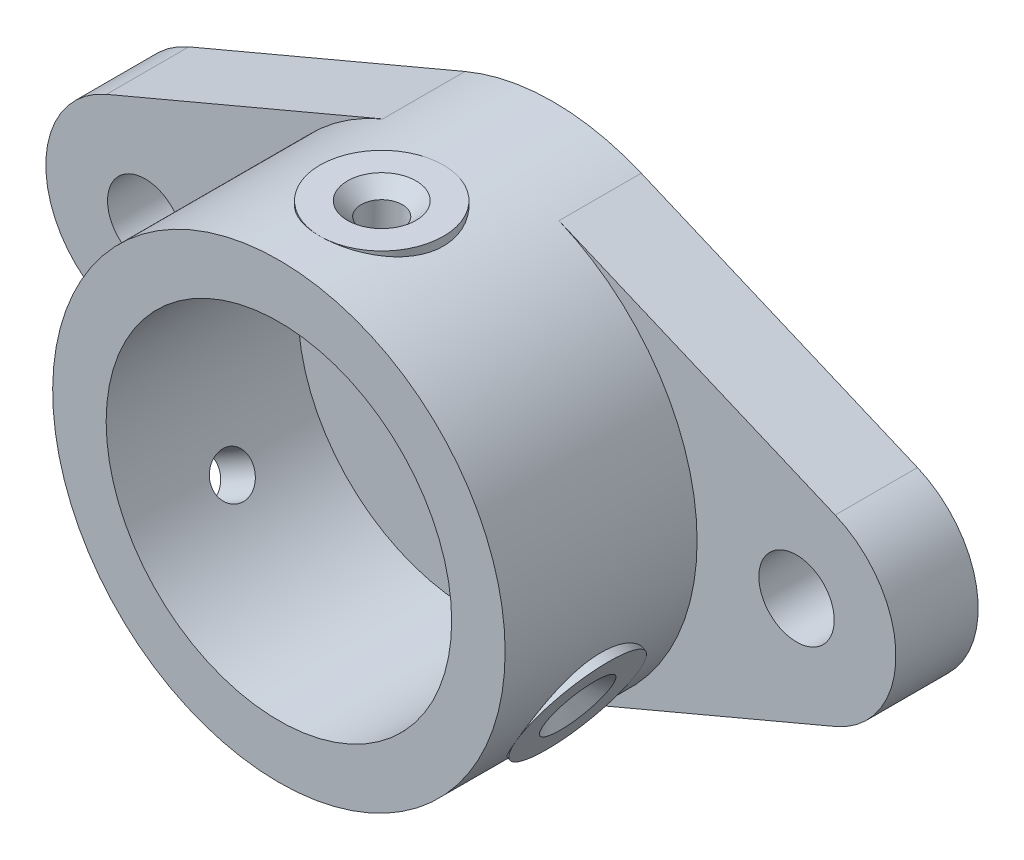
SolidWorks part; units mm, degrees
ref_plane "Front Plane" through (0, 0, 0) normal (0, 0, 1) x (1, 0, 0)
ref_plane "Top Plane" through (0, 0, 0) normal (0, 1, 0) x (1, 0, 0)
ref_plane "Right Plane" through (0, 0, 0) normal (1, 0, 0) x (0, 0, -1)
sketch "Sketch1" plane through (0, 0, 0) normal (0, 0, 1) x (1, 0, 0)
  circle A0 centre (0, 0) radius 12.6
  circle A1 centre (0, 0) radius 16.5
  dimension "D1" = 25.2
  dimension "D2" = 33
extrude "Boss-Extrude1" add sketch "Sketch1" along normal blind 15
sketch "Sketch2" plane through (0, 0, 0) normal (0, 0, -1) x (-1, 0, 0)
  circle A0 centre (0, 0) radius 16.5
  circle A1 centre (0, 0) radius 16.5 construction
extrude "Boss-Extrude2" add sketch "Sketch2" along normal blind 5
ref_plane "Plane1" through (0, 16.5, 0) normal (0, 1, 0) x (1, 0, 0)
sketch "Sketch3" plane through (0, 16.5, 0) normal (0, 1, 0) x (1, 0, 0)
  line L0 (-16.5, -15) -> (16.5, -15) construction
  circle A0 centre (0, -7.5) radius 4.5
  dimension "D1" = 9
  dimension "D2" = 7.5
extrude "Boss-Extrude3" add sketch "Sketch3" against normal up to surface up to face at (16.5, 0, 15)
sketch "Sketch4" plane through (0, 16.5, 0) normal (0, 1, 0) x (1, 0, 0)
  line L0 (-16.5, -15) -> (16.5, -15) construction
  circle A0 centre (0, -7.5) radius 1.5
  dimension "D1" = 3
  dimension "D2" = 7.5
extrude "Cut-Extrude1" cut sketch "Sketch4" against normal up to surface (3.9 mm away) up to face at (12.6, 0, 15)
pattern_circular "CirPattern1" count 3 over 360 about axis through (0, 0, 15) along (0, 0, 1) of "Cut-Extrude1", "Boss-Extrude3"
chamfer "Chamfer1" distance 1 angle 45 3 edges at (-14.2894, -8.25, 9) (14.2894, -8.25, 9) (0, 16.5, 9)
sketch "Sketch5" plane through (0, 0, -5) normal (0, 0, -1) x (-1, 0, 0)
  line L0 (26.5737, 6.6775) -> (6.4263, 15.1971)
  line L1 (26.5737, -6.6775) -> (6.4263, -15.1971)
  line L2 (-6.4263, 15.1971) -> (-26.5737, 6.6775)
  line L3 (-6.4263, -15.1971) -> (-26.5737, -6.6775)
  circle A0 centre (23.75, 0) radius 2.75
  circle A1 centre (-23.75, 0) radius 2.75
  arc A2 (26.5737, -6.6775) -> (26.5737, 6.6775) centre (23.75, 0) ccw
  arc A3 (-26.5737, 6.6775) -> (-26.5737, -6.6775) centre (-23.75, 0) ccw
  circle A4 centre (0, 0) radius 16.5 construction
  circle A6 centre (0, 0) radius 16.5 construction
  circle A8 centre (0, 0) radius 16.5 construction
  arc A9 (6.4263, 15.1971) -> (-6.4263, 15.1971) centre (0, 0) ccw
  arc A10 (6.4263, -15.1971) -> (-6.4263, -15.1971) centre (0, 0) cw
  dimension "D3" = 5.5
  dimension "D1" = 23.75
  dimension "D2" = 23.75
extrude "Boss-Extrude4" add sketch "Sketch5" against normal blind 6
sketch "Sketch6" plane through (0, 0, 1) normal (0, 0, 1) x (1, 0, 0)
  circle A0 centre (-23.75, 0) radius 4.5
  circle A1 centre (23.75, 0) radius 4.5
  dimension "D1" = 9
extrude "Cut-Extrude2" [suppressed] cut sketch "Sketch6" against normal blind 5
